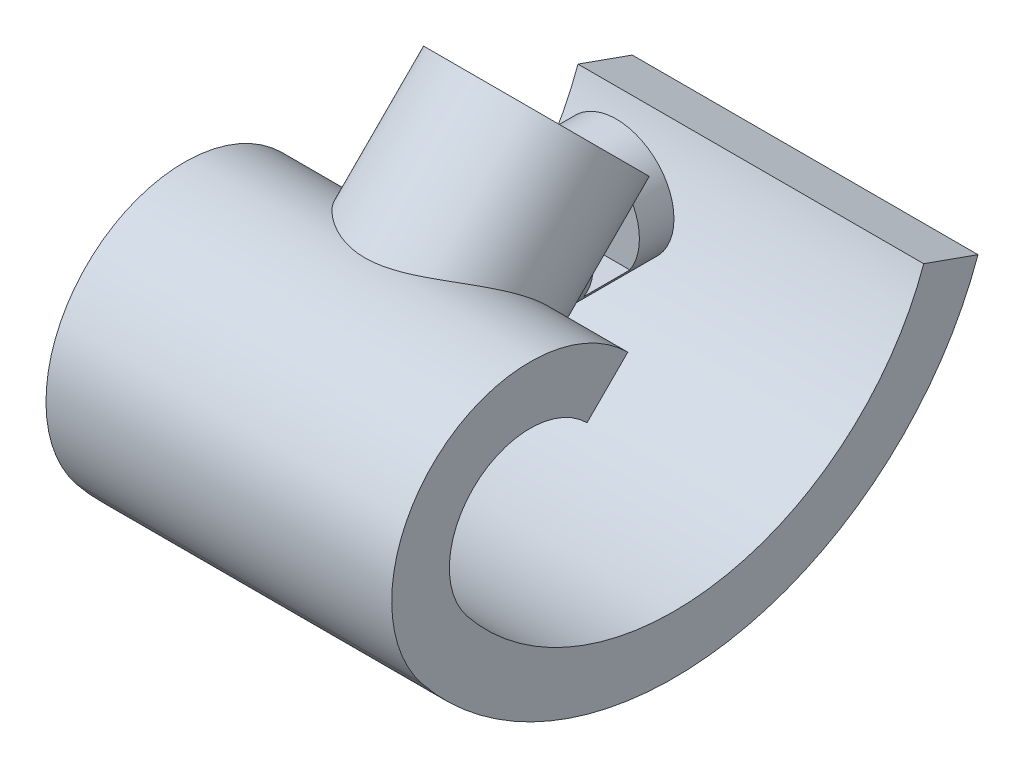
SolidWorks part; units mm, degrees
ref_plane "Спереди" through (0, 0, 0) normal (0, 0, 1) x (1, 0, 0)
ref_plane "Сверху" through (0, 0, 0) normal (0, 1, 0) x (1, 0, 0)
ref_plane "Справа" through (0, 0, 0) normal (1, 0, 0) x (0, 0, -1)
sketch "Sketch1" plane through (0, 0, 0) normal (1, 0, 0) x (0, 0, -1)
  line L0 (-4.0047, 8.4853) -> (-12.49, 0) construction
  line L1 (-12.49, 0) -> (-12.49, 19.5798) construction
  arc A0 (-21.8575, -7.5) -> (26.3823, 0.6205) centre (0, 10) ccw
  arc A1 (-21.8575, -7.5) -> (-4.0047, 8.4853) centre (-12.49, 0) cw
  dimension "D1" = 28
  dimension "D3" = 12
  dimension "D2" = 10
  dimension "D4" = 45
extrude "Extrude-Thin1" add sketch "Sketch1" along normal mid plane 30 thin thin type one direction wall 5
sketch "Sketch2" plane through (0, 0, 0) normal (1, 0, 0) x (0, 0, -1)
  line L0 (-12.49, 0) -> (-4.0047, 8.4853) construction
  line L1 (-4.0047, 8.4853) -> (-12.0252, 16.5058) construction
ref_plane "Plane1" through (0, 2.2403, -2.2403) normal (0, 0.7071, -0.7071) x (1, 0, 0)
sketch "Sketch3" plane through (0, 2.2403, -2.2403) normal (0, 0.7071, -0.7071) x (1, 0, 0)
  line L0 (15, -8.8318) -> (-15, -8.8318) construction
  circle A0 centre (0, -8.8318) radius 4
  circle A1 centre (0, -8.8318) radius 8
  dimension "D1" = 8
  dimension "D2" = 4
extrude "Boss-Extrude1" add sketch "Sketch3" along normal blind 10 and the other way blind 5
sketch "Sketch5" plane through (0, 0, 0) normal (0, 0, 1) x (1, 0, 0)
  circle A0 centre (0, 6.5) radius 5
  dimension "D1" = 10
  dimension "D2" = 6.5
extrude "Boss-Extrude2" add sketch "Sketch5" against normal blind 10
sketch "Sketch6" plane through (0, 0, -10) normal (0, 0, -1) x (-1, 0, 0)
  circle A0 centre (0, 6.5) radius 1.5
  dimension "D1" = 3
extrude "Cut-Extrude2" cut sketch "Sketch6" against normal blind 14
sketch "Sketch4" plane through (0, 9.3114, -9.3114) normal (0, 0.7071, -0.7071) x (1, 0, 0)
  circle A0 centre (0, -8.8318) radius 4
  circle A1 centre (0, -8.8318) radius 4 construction
extrude "Cut-Extrude1" cut sketch "Sketch4" against normal blind 20
ref_plane "Plane2" through (0, 0, -7) normal (0, 0, -1) x (-1, 0, 0)
sketch "Sketch7" plane through (0, 0, -7) normal (0, 0, -1) x (-1, 0, 0)
  line L0 (-1.5877, 9.25) -> (-18.5606, 9.25)
  line L1 (3.1754, 6.5) -> (1.5877, 9.25)
  line L2 (1.5877, 9.25) -> (-1.5877, 9.25)
  line L3 (-1.5877, 9.25) -> (-3.1754, 6.5)
  line L4 (-3.1754, 6.5) -> (-1.5877, 3.75)
  line L5 (-1.5877, 3.75) -> (1.5877, 3.75)
  line L6 (1.5877, 3.75) -> (3.1754, 6.5)
  line L7 (-18.5606, 9.25) -> (-18.5606, 3.75)
  line L8 (-18.5606, 3.75) -> (-1.5877, 3.75)
  circle A0 centre (0, 6.5) radius 2.75 construction
  dimension "D1" = 5.5
extrude "Cut-Extrude3" cut sketch "Sketch7" against normal blind 3 contours L5 L6 L1 L2 L3 L4 | L7 L8 L4 L3 L0 region at (10.4646, 6.5, -7) region at (0, 6.5, -7)
chamfer "Chamfer1" distance 1 angle 45 1 edges at (4.9131, 5.5719, -4)
